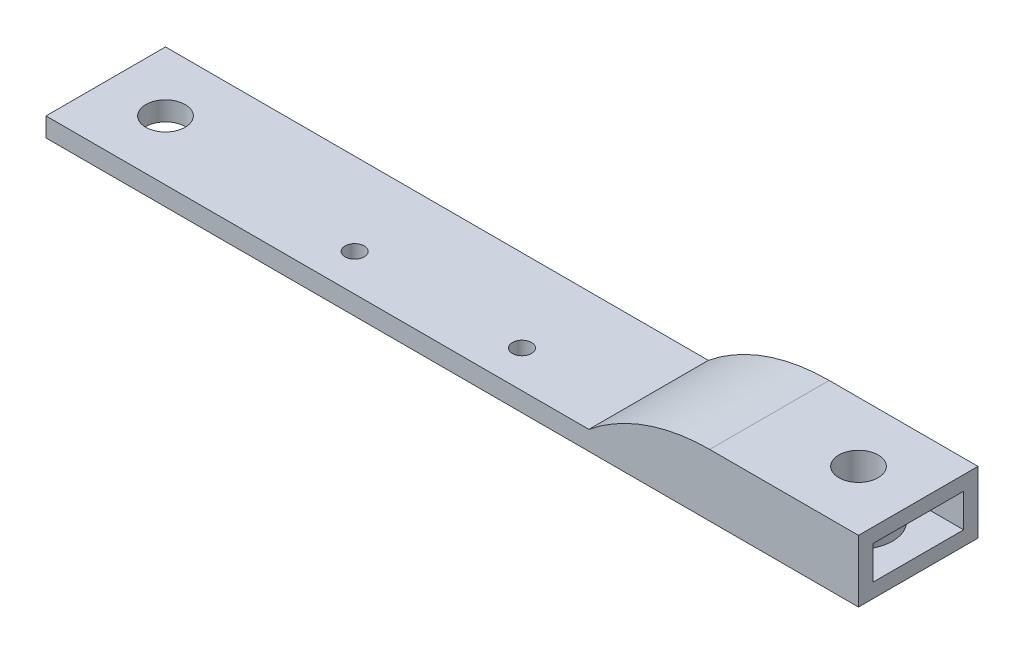
SolidWorks part; units mm, degrees
ref_plane "Front Plane" through (0, 0, 0) normal (0, 0, 1) x (1, 0, 0)
ref_plane "Top Plane" through (0, 0, 0) normal (0, 1, 0) x (1, 0, 0)
ref_plane "Right Plane" through (0, 0, 0) normal (1, 0, 0) x (0, 0, -1)
sketch "Sketch1" plane through (0, 0, 0) normal (0, 1, 0) x (1, 0, 0)
  line L1 (-85, 12.5) -> (85, 12.5)
  line L2 (-85, 12.5) -> (-85, -12.5)
  line L3 (-85, -12.5) -> (85, -12.5)
  line L4 (85, 12.5) -> (85, -12.5)
  line L5 (-85, 12.5) -> (85, -12.5) construction
  line L6 (-85, -12.5) -> (85, 12.5) construction
  circle A0 centre (-10.6801, 3.3392) radius 4.5
  circle A1 centre (-10.6585, -3.6607) radius 14
  circle A2 centre (-28.1585, -4.7634) radius 2
  circle A3 centre (6.8415, -4.7634) radius 2
  circle A4 centre (72.5, 0) radius 4.125
  point P0 (0, 0)
  point P17 (85, 0)
  dimension "D3" = 12.5
  dimension "D4" = 4
  dimension "D5" = 4
  dimension "D6" = 8.25
  dimension "D7" = 7.7366
  dimension "D1" = 25
  dimension "D2" = 170
extrude "Boss-Extrude1" add sketch "Sketch1" along normal blind 4 contours A1 L3 L4 L1 L2 A4 A3 A2 | L3 A1 A0 | A0 region at (0, 0, -10.7817) region at (-10.6556, 0, 2.8007)
sketch "Sketch2" plane through (0, 4, 0) normal (0, 1, 0) x (1, 0, 0)
  line L0 (-85, 12.5) -> (-85, -12.5) construction
  circle A0 centre (-72.5, 0) radius 4.125
  circle A1 centre (-72.5, 0) radius 20 construction
  circle A2 centre (-42.5, 0) radius 10 construction
  dimension "D1" = 8.25
  dimension "D2" = 12.5
extrude "Cut-Extrude1" cut sketch "Sketch2" against normal through all
sketch "Sketch3" plane through (0, 4, 0) normal (0, 1, 0) x (1, 0, 0)
  line L0 (28.5855, 12.5) -> (28.5855, -12.5)
  line L1 (-85, 12.5) -> (85, 12.5) construction
  line L2 (-85, -12.5) -> (85, -12.5) construction
  line L3 (28.5855, -12.5) -> (85, -12.5)
  line L4 (85, -12.5) -> (85, 12.5)
  line L5 (85, 12.5) -> (28.5855, 12.5)
  circle A0 centre (72.5, 0) radius 4.125
extrude "Boss-Extrude2" add sketch "Sketch3" along normal blind 9
sketch "Sketch4" plane through (0, 13, 0) normal (0, 1, 0) x (1, 0, 0)
  line L4 (85, -12.5) -> (85, 12.5)
  line L6 (85, 12.5) -> (60, 12.5)
  line L7 (85, 12.5) -> (28.5855, 12.5) construction
  line L8 (60, 12.5) -> (60, -12.5)
  line L9 (28.5855, -12.5) -> (85, -12.5) construction
  line L10 (60, -12.5) -> (85, -12.5)
  circle A0 centre (72.5, 0) radius 4.125
  dimension "D1" = 25
fillet "Fillet1" radius 40 1 edges at (28.5855, 13, 0)
sketch "Sketch5" plane through (0, 0, 12.5) normal (0, 0, 1) x (1, 0, 0)
  line L0 (85, 19.6943) -> (60.9639, 19.6943)
  line L1 (85, 13) -> (85, 0) construction
  line L2 (32.6181, 4) -> (85, 4)
  line L3 (85, 4) -> (85, 19.6943)
  spline S0 degree 2 poles (32.6181, 4) (45.2561, 17.208) (60.9639, 19.6943) knots 0 0 0 0.765358 0.765358 0.765358
shell "Shell2" thickness 3 removed face at (85, 6.5, 0)
